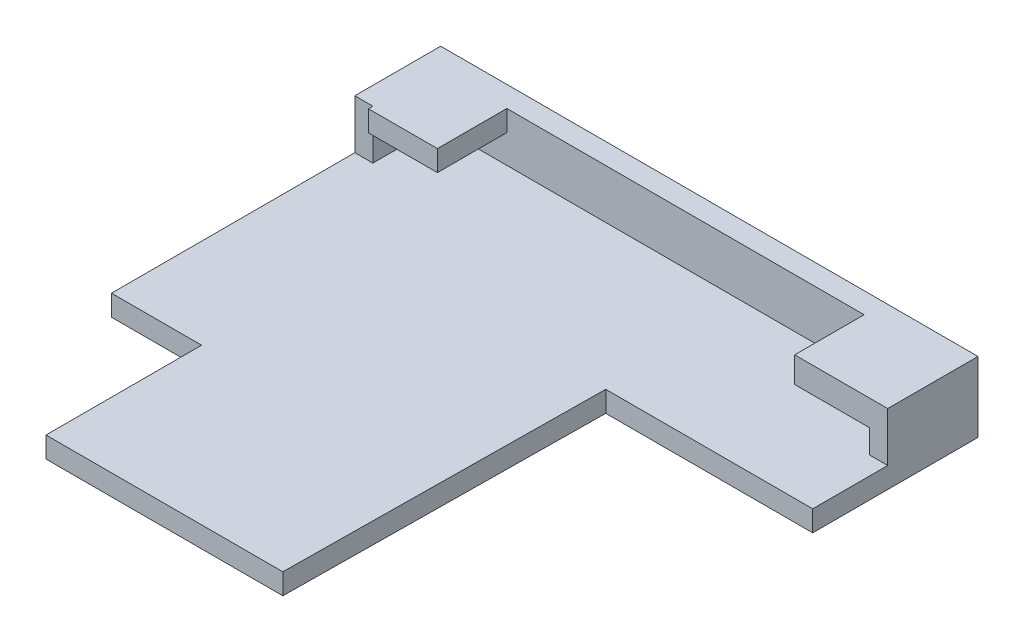
SolidWorks part; units mm, degrees
ref_plane "Front Plane" through (0, 0, 0) normal (0, 0, 1) x (1, 0, 0)
ref_plane "Top Plane" through (0, 0, 0) normal (0, 1, 0) x (1, 0, 0)
ref_plane "Right Plane" through (0, 0, 0) normal (1, 0, 0) x (0, 0, -1)
sketch "Sketch1" plane through (0, 0, 0) normal (0, 1, 0) x (1, 0, 0)
  line L0 (-75.3391, 34.6839) -> (-39.6391, 34.6839)
  line L2 (-75.3391, 34.6839) -> (-75.3391, 24.2839)
  line L8 (-75.3391, 24.2839) -> (-75.3391, 12.4839)
  line L9 (-75.3391, 12.4839) -> (-70.3391, 12.4839)
  line L10 (-70.3391, 12.4839) -> (-70.3391, 1.2839)
  line L11 (-39.6391, 34.6839) -> (-39.6391, 24.2839)
  line L12 (-39.6391, 24.2839) -> (-53.0391, 24.2839)
  line L13 (-53.0391, 24.2839) -> (-53.2891, 1.2839)
  line L14 (-70.3391, 1.2839) -> (-53.2891, 1.2839)
extrude "Boss-Extrude1" add sketch "Sketch1" along normal blind 1.5
sketch "Sketch2" plane through (0, 0, -34.6839) normal (0, 0, -1) x (-1, 0, 0)
  line L0 (18.37, 0) -> (-18.37, 0) construction
  line L1 (39.6391, 1.5) -> (75.3259, 1.5)
  line L2 (39.6391, 1.5) -> (39.6391, 0)
  line L3 (39.6391, 0) -> (75.3259, 0)
  line L4 (75.3259, 1.5) -> (75.3259, 0)
extrude "Boss-Extrude2" add sketch "Sketch2" along normal blind 1.5
sketch "Sketch3" plane through (-39.6391, 0, 0) normal (1, 0, 0) x (0, 0, -1)
  line L0 (19.195, 0) -> (-19.195, 0) construction
  line L1 (24.2839, 1.5) -> (36.1839, 1.5)
  line L2 (24.2839, 1.5) -> (24.2839, 0)
  line L3 (24.2839, 0) -> (36.1839, 0)
  line L4 (36.1839, 1.5) -> (36.1839, 0)
  line L5 (36.1839, 1.5) -> (36.1839, 0) construction
extrude "Boss-Extrude3" add sketch "Sketch3" along normal blind 1.5
sketch "Sketch4" plane through (-75.3259, 0, 0) normal (-1, 0, 0) x (0, 0, 1)
  line L0 (19.195, 0) -> (-19.195, 0) construction
  line L1 (-36.1839, 1.5) -> (-12.4839, 1.5)
  line L2 (-36.1839, 1.5) -> (-36.1839, 0)
  line L3 (-36.1839, 0) -> (-12.4839, 0)
  line L4 (-12.4839, 1.5) -> (-12.4839, 0)
  dimension "D1" = 23.7
extrude "Boss-Extrude4" add sketch "Sketch4" along normal blind 1.5
sketch "Sketch5" plane through (0, 1.5, 0) normal (0, 1, 0) x (1, 0, 0)
  line L0 (-76.8259, 12.4839) -> (-75.5259, 12.4839) construction
  line L1 (-76.8259, 12.4839) -> (-70.3391, 12.4839) construction
  line L2 (-75.5259, 36.1839) -> (-75.5259, 34.6839) construction
  line L3 (-76.8259, 36.1839) -> (-38.1391, 36.1839) construction
  line L4 (-38.1391, 34.6839) -> (-39.4391, 34.6839) construction
  line L5 (-38.1391, 36.1839) -> (-38.1391, 24.2839) construction
  line L6 (-39.4391, 24.2839) -> (-39.4391, 25.7839) construction
  line L7 (-53.0391, 24.2839) -> (-38.1391, 24.2839) construction
  line L8 (-76.8259, 35.0042) -> (-76.8259, 30.0042) construction
  line L9 (-76.8259, 12.4839) -> (-76.8259, 36.1839) construction
  line L10 (-75.5259, 34.6839) -> (-75.5259, 30.0042)
  line L11 (-75.5259, 30.0042) -> (-76.8259, 30.0042)
  line L12 (-76.8259, 30.0042) -> (-76.8259, 36.1839)
  line L13 (-76.8259, 36.1839) -> (-70.5592, 36.1839)
  line L14 (-70.5592, 36.1839) -> (-70.5592, 34.6839)
  line L15 (-70.5592, 34.6839) -> (-75.5259, 34.6839)
  line L16 (-39.4391, 34.6839) -> (-39.4391, 29.6839)
  line L17 (-39.4391, 29.6839) -> (-38.1391, 29.6839)
  line L18 (-38.1391, 29.6839) -> (-38.1391, 36.1839)
  line L19 (-38.1391, 36.1839) -> (-44.8391, 36.1839)
  line L20 (-44.8391, 36.1839) -> (-44.8391, 34.6839)
  line L21 (-44.8391, 34.6839) -> (-39.4391, 34.6839)
  dimension "D1" = 1.3
  dimension "D2" = 1.3
extrude "Boss-Extrude5" add sketch "Sketch5" along normal blind 3.55
sketch "Sketch6" plane through (0, 0, -34.6839) normal (0, 0, 1) x (1, 0, 0)
  line L0 (-70.5592, 5.05) -> (-70.5592, 1.5) construction
  line L1 (-75.5259, 5.05) -> (-70.5592, 5.05)
  line L2 (-75.5259, 5.05) -> (-75.5259, 3.55)
  line L3 (-75.5259, 3.55) -> (-70.5592, 3.55)
  line L4 (-70.5592, 5.05) -> (-70.5592, 3.55)
  line L5 (-39.4391, 5.05) -> (-39.4391, 1.5) construction
  line L6 (-44.8391, 5.05) -> (-39.4391, 5.05)
  line L7 (-44.8391, 5.05) -> (-44.8391, 3.2)
  line L8 (-44.8391, 3.2) -> (-39.4391, 3.2)
  line L9 (-39.4391, 5.05) -> (-39.4391, 3.2)
  dimension "D1" = 1.5
extrude "Boss-Extrude6" add sketch "Sketch6" along normal blind 5
sketch "Sketch7" plane through (0, 1.5, 0) normal (0, 1, 0) x (1, 0, 0)
  line L0 (-70.5592, 36.1839) -> (-70.5592, 34.6839)
  line L1 (-70.5592, 34.6839) -> (-44.8391, 34.6839)
  line L2 (-44.8391, 34.6839) -> (-44.8391, 36.1839)
  line L3 (-44.8391, 36.1839) -> (-70.5592, 36.1839)
extrude "Boss-Extrude7" add sketch "Sketch7" along normal blind 3.55
